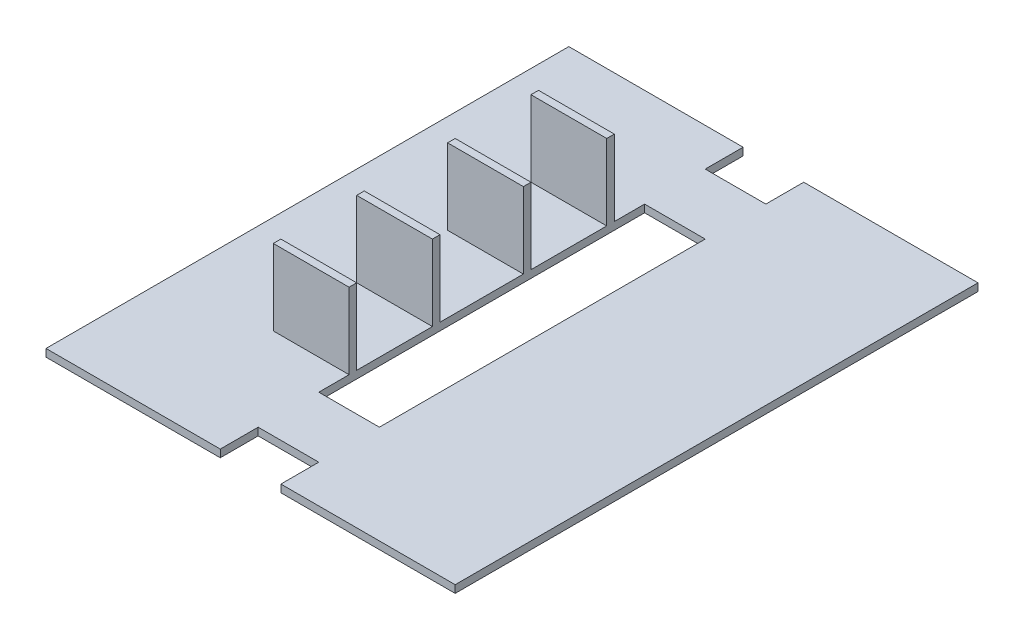
SolidWorks part; units mm, degrees
ref_plane "Front Plane" through (0, 0, 0) normal (0, 0, 1) x (1, 0, 0)
ref_plane "Top Plane" through (0, 0, 0) normal (0, 1, 0) x (1, 0, 0)
ref_plane "Right Plane" through (0, 0, 0) normal (1, 0, 0) x (0, 0, -1)
sketch "Sketch1" plane through (0, 0, 0) normal (0, 1, 0) x (1, 0, 0)
  line L0 (115, 320) -> (115, 345)
  line L1 (0, 0) -> (115, 0)
  line L2 (0, 0) -> (0, 345)
  line L3 (0, 345) -> (115, 345)
  line L4 (115, 0) -> (115, 25)
  line L5 (155, 345) -> (270, 345)
  line L6 (155, 345) -> (155, 320)
  line L7 (155, 0) -> (270, 0)
  line L8 (270, 345) -> (270, 0)
  line L9 (115, 320) -> (155, 320)
  line L11 (115, 280) -> (155, 280)
  line L13 (115, 65) -> (155, 65)
  line L15 (115, 25) -> (155, 25)
  line L17 (155, 280) -> (155, 65)
  line L18 (115, 65) -> (115, 280)
  line L19 (155, 25) -> (155, 0)
  line L20 (115, 320) -> (115, 280) construction
  line L21 (115, 65) -> (115, 25) construction
  dimension "D1" = 345
  dimension "D2" = 270
  dimension "D3" = 40
  dimension "D4" = 40
  dimension "D5" = 25
extrude "Boss-Extrude1" add sketch "Sketch1" along normal blind 5
sketch "Sketch2" plane through (0, 5, 0) normal (0, 1, 0) x (1, 0, 0)
  line L1 (65, 260) -> (115, 260)
  line L2 (65, 260) -> (65, 255)
  line L3 (65, 255) -> (115, 255)
  line L4 (115, 260) -> (115, 255)
  line L5 (65, 205) -> (115, 205)
  line L6 (65, 205) -> (65, 200)
  line L7 (65, 200) -> (115, 200)
  line L8 (115, 205) -> (115, 200)
  line L9 (115, 280) -> (115, 65) construction
  line L10 (115, 172.5) -> (155, 172.5) construction
  line L11 (155, 65) -> (155, 280) construction
  line L12 (65, 145) -> (115, 145)
  line L13 (115, 140) -> (115, 145)
  line L14 (65, 140) -> (115, 140)
  line L15 (65, 140) -> (65, 145)
  line L16 (65, 90) -> (115, 90)
  line L17 (115, 85) -> (115, 90)
  line L18 (65, 85) -> (115, 85)
  line L19 (65, 85) -> (65, 90)
  point P22 (0, 0)
  dimension "D1" = 5
  dimension "D2" = 50
  dimension "D3" = 50
  dimension "D4" = 55
extrude "Boss-Extrude2" add sketch "Sketch2" along normal blind 50
